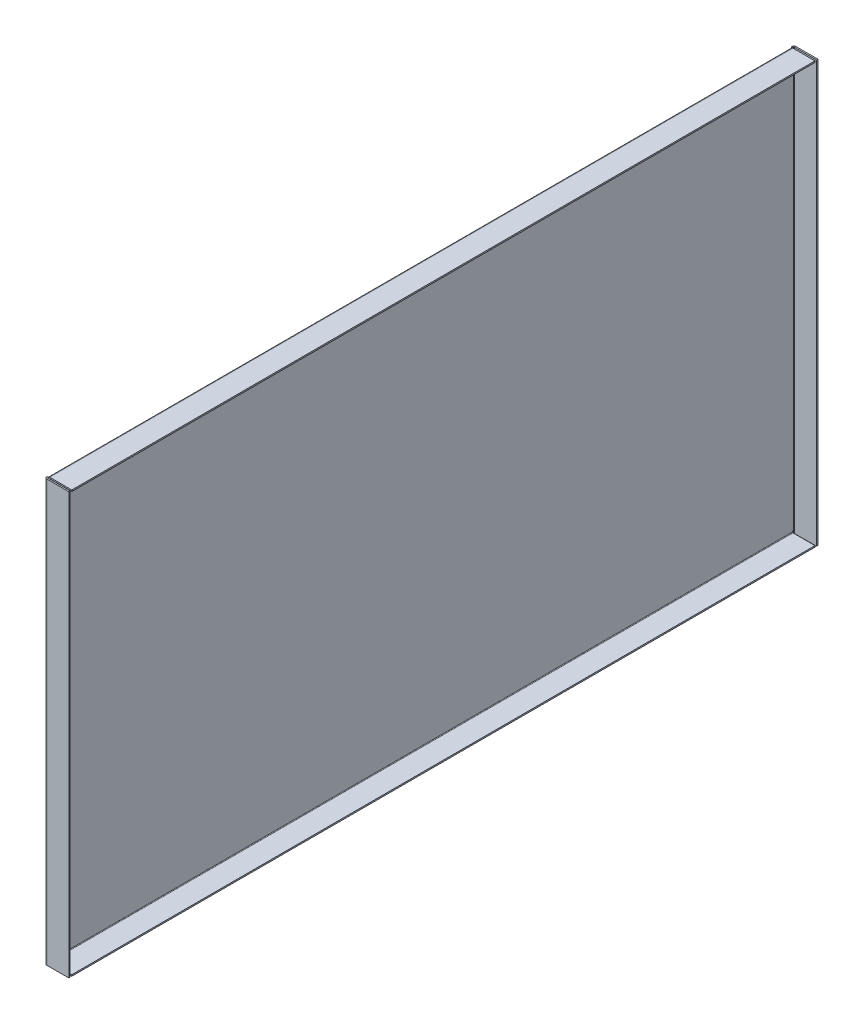
SolidWorks part; units mm, degrees
note: The reader was unsure of these and kept them because the rebuilt part matched: flange length of "Edge-Flange1", "Edge-Flange2", "Edge-Flange4", "Edge-Flange5".
ref_plane "Front Plane" through (0, 0, 0) normal (0, 0, 1) x (1, 0, 0)
ref_plane "Top Plane" through (0, 0, 0) normal (0, 1, 0) x (1, 0, 0)
ref_plane "Right Plane" through (0, 0, 0) normal (1, 0, 0) x (0, 0, -1)
sketch "Sketch1" plane through (0, 0, 0) normal (1, 0, 0) x (0, 0, -1)
  line L1 (-467.85, -264) -> (467.85, -264)
  line L2 (-467.85, -264) -> (-467.85, 264)
  line L3 (-467.85, 264) -> (467.85, 264)
  line L4 (467.85, -264) -> (467.85, 264)
  line L5 (-467.85, -264) -> (467.85, 264) construction
  line L6 (-467.85, 264) -> (467.85, -264) construction
  point P0 (0, 0)
  dimension "D1" = 528
  dimension "D2" = 935.7
base flange "Base-Flange1" sketch "Sketch1" thickness 1.7366 reverse thickness direction no parameters "D1"=0.7366
edge flange "Edge-Flange1" sketch "Sketch8" flange angle 90 flange length 30 flange position material inside bend radius 0.7366 thickness 1.7366 relief rectangular parameters "D6"=10
sketch "Sketch8" plane through (0, 264, 0) normal (0, 1, 0) x (0, 0, 1)
  line L2 (-465.85, 0) -> (-465.85, 28.2634)
  line L3 (-465.85, 28.2634) -> (465.85, 28.2634)
  line L4 (465.85, 28.2634) -> (465.85, 0)
  line L5 (-467.85, 0) -> (467.85, 0) construction
  line L6 (-465.85, 0) -> (465.85, 0)
  dimension "D1" = 2
  dimension "D2" = 2
bend "EdgeBend1" bend radius 0.7366 bend angle 90 parameters "D5"=1
edge flange "Edge-Flange2" sketch "Sketch11" flange angle 90 flange length 30 flange position material inside bend radius 0.7366 thickness 1.7366 relief rectangular parameters "D6"=10
sketch "Sketch11" plane through (0, -264, 0) normal (0, -1, 0) x (0, 0, -1)
  line L0 (-467.85, 0) -> (467.85, 0) construction
  line L1 (-465.85, 0) -> (465.85, 0)
  line L2 (-465.85, 0) -> (-465.85, 28.2634)
  line L3 (-465.85, 28.2634) -> (465.85, 28.2634)
  line L4 (465.85, 28.2634) -> (465.85, 0)
  dimension "D1" = 2
  dimension "D2" = 2
bend "EdgeBend2" bend radius 0.7366 bend angle 90 parameters "D5"=2
edge flange "Edge-Flange4" sketch "Sketch15" flange angle 90 flange length 30 flange position material outside bend radius 0.7366 thickness 1.7366 relief rectangular parameters "D6"=10
sketch "Sketch15" plane through (0, 0, 467.85) normal (0, 0, 1) x (0, -1, 0)
  line L0 (-264, 0) -> (264, 0) construction
  line L1 (-264, 0) -> (264, 0)
  line L2 (-264, 0) -> (-264, 28.2634)
  line L3 (-264, 28.2634) -> (264, 28.2634)
  line L4 (264, 28.2634) -> (264, 0)
bend "EdgeBend4" bend radius 0.7366 bend angle 90 parameters "D5"=3
edge flange "Edge-Flange5" sketch "Sketch18" flange angle 90 flange length 30 flange position material outside bend radius 0.7366 thickness 1.7366 relief rectangular parameters "D6"=10
sketch "Sketch18" plane through (0, 0, -467.85) normal (0, 0, -1) x (0, 1, 0)
  line L0 (-264, 0) -> (264, 0) construction
  line L1 (-264, 0) -> (264, 0)
  line L2 (-264, 0) -> (-264, 28.2634)
  line L3 (-264, 28.2634) -> (264, 28.2634)
  line L4 (264, 28.2634) -> (264, 0)
bend "EdgeBend5" bend radius 0.7366 bend angle 90 parameters "D5"=4
sketch "Bend-Lines1" [suppressed] plane through (0, 0, 0) normal (0, 1, 0) x (1, 0, 0)
sketch "Bounding-Box1" [suppressed] plane through (0, 0, 0) normal (0, 1, 0) x (1, 0, 0)
sheet metal parameters "Sheet-Metal1" thickness 1.7366 parameters "D1"=0.7366
flat pattern "Flat-Pattern1" [suppressed]
sketch "Bend-Lines2" plane through (0, 0, 0) normal (0, 1, 0) x (1, 0, 0)
sketch3d "Bounding-Box2" [suppressed]
  line L0 (-469.85, -264, 0) -> (469.85, -264, 0) construction
  line L1 (-469.85, 264, 0) -> (469.85, 264, 0) construction
  line L2 (-469.85, -264, 0) -> (-469.85, 264, 0) construction
  line L3 (469.85, -264, 0) -> (469.85, 264, 0) construction
sheet metal parameters "Sheet-Metal2" thickness 1.7366 parameters "D1"=0.7366
flat pattern "Flat-Pattern1"
sketch "Bend-Lines2" plane through (0, 0, 0) normal (1, 0, 0) x (0, 0, -1)
  line L0 (469.85, 262.7873) -> (-469.85, 262.7873) construction
  line L1 (469.85, 262.7873) -> (-469.85, 262.7873) construction
sketch3d "Bounding-Box2" [suppressed]
  line L0 (469.85, -264, 0) -> (-469.85, -264, 0) construction
  line L1 (469.85, 291.5746, 0) -> (-469.85, 291.5746, 0) construction
  line L2 (469.85, -264, 0) -> (469.85, 291.5746, 0) construction
  line L3 (-469.85, -264, 0) -> (-469.85, 291.5746, 0) construction
bend of the flat pattern "Flatten-<EdgeBend1>1"
sheet metal parameters "Sheet-Metal3" thickness 1.7366 parameters "D1"=0.7366
flat pattern "Flat-Pattern1"
sketch "Bend-Lines2" plane through (0, 0, 0) normal (1, 0, 0) x (0, 0, -1)
  line L0 (467.85, 262.7873) -> (-467.85, 262.7873) construction
  line L1 (467.85, 262.7873) -> (-467.85, 262.7873) construction
  line L2 (-467.85, -262.7873) -> (467.85, -262.7873) construction
  line L3 (-467.85, -262.7873) -> (467.85, -262.7873) construction
sketch3d "Bounding-Box2" [suppressed]
  line L0 (469.85, -291.5746, 0) -> (-469.85, -291.5746, 0) construction
  line L1 (469.85, 291.5746, 0) -> (-469.85, 291.5746, 0) construction
  line L2 (469.85, -291.5746, 0) -> (469.85, 291.5746, 0) construction
  line L3 (-469.85, -291.5746, 0) -> (-469.85, 291.5746, 0) construction
bend of the flat pattern "Flatten-<EdgeBend1>1"
bend of the flat pattern "Flatten-<EdgeBend2>1"
sheet metal parameters "Sheet-Metal4" thickness 1.7366 parameters "D1"=0.7366
flat pattern "Flat-Pattern1"
sketch "Bend-Lines2" plane through (0, 0, 0) normal (1, 0, 0) x (0, 0, -1)
  line L0 (467.85, 262.7873) -> (-467.85, 262.7873) construction
  line L1 (467.85, 262.7873) -> (-467.85, 262.7873) construction
  line L2 (-467.85, -262.7873) -> (467.85, -262.7873) construction
  line L3 (-467.85, -262.7873) -> (467.85, -262.7873) construction
  line L4 (-470.3739, 264) -> (-470.3739, -264) construction
  line L5 (-470.3739, 264) -> (-470.3739, -264) construction
sketch3d "Bounding-Box2" [suppressed]
  line L0 (469.85, -291.5746, 0) -> (-499.1612, -291.5746, 0) construction
  line L1 (469.85, 291.5746, 0) -> (-499.1612, 291.5746, 0) construction
  line L2 (469.85, -291.5746, 0) -> (469.85, 291.5746, 0) construction
  line L3 (-499.1612, -291.5746, 0) -> (-499.1612, 291.5746, 0) construction
bend of the flat pattern "Flatten-<EdgeBend1>1"
bend of the flat pattern "Flatten-<EdgeBend2>1"
bend of the flat pattern "Flatten-<EdgeBend4>1"
sheet metal parameters "Sheet-Metal5" thickness 1.7366 parameters "D1"=0.7366
flat pattern "Flat-Pattern1"
sketch "Bend-Lines2" plane through (0, 0, 0) normal (1, 0, 0) x (0, 0, -1)
  line L0 (465.85, 262.7873) -> (-465.85, 262.7873) construction
  line L1 (465.85, 262.7873) -> (-465.85, 262.7873) construction
  line L2 (-465.85, -262.7873) -> (465.85, -262.7873) construction
  line L3 (-465.85, -262.7873) -> (465.85, -262.7873) construction
  line L4 (-468.3739, 264) -> (-468.3739, -264) construction
  line L5 (-468.3739, 264) -> (-468.3739, -264) construction
  line L6 (468.3739, -264) -> (468.3739, 264) construction
  line L7 (468.3739, -264) -> (468.3739, 264) construction
sketch3d "Bounding-Box2" [suppressed]
  line L0 (497.1612, -291.5746, 0) -> (-497.1612, -291.5746, 0) construction
  line L1 (497.1612, 291.5746, 0) -> (-497.1612, 291.5746, 0) construction
  line L2 (497.1612, -291.5746, 0) -> (497.1612, 291.5746, 0) construction
  line L3 (-497.1612, -291.5746, 0) -> (-497.1612, 291.5746, 0) construction
bend of the flat pattern "Flatten-<EdgeBend1>1"
bend of the flat pattern "Flatten-<EdgeBend2>1"
bend of the flat pattern "Flatten-<EdgeBend4>1"
bend of the flat pattern "Flatten-<EdgeBend5>1"
